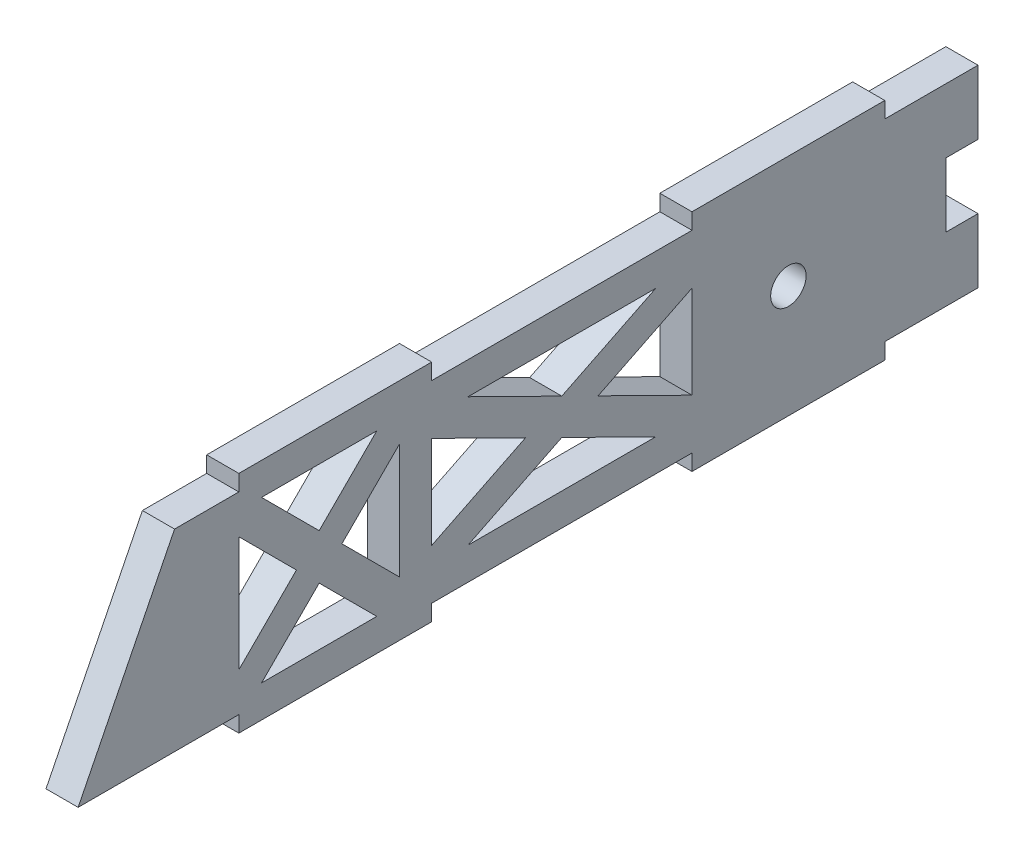
SolidWorks part; units mm, degrees
material "7050-T73510"
ref_plane "Front Plane" through (0, 0, 0) normal (0, 0, 1) x (1, 0, 0)
ref_plane "Top Plane" through (0, 0, 0) normal (0, 1, 0) x (1, 0, 0)
ref_plane "Right Plane" through (0, 0, 0) normal (1, 0, 0) x (0, 0, -1)
sketch "Sketch1" plane through (0, 0, 0) normal (1, 0, 0) x (0, 0, -1)
  line L1 (-177.8, -38.1) -> (177.8, -38.1)
  line L2 (-177.8, -38.1) -> (-177.8, 38.1)
  line L3 (-177.8, 38.1) -> (177.8, 38.1)
  line L4 (177.8, -38.1) -> (177.8, 38.1)
  line L5 (-177.8, -38.1) -> (177.8, 38.1) construction
  line L6 (-177.8, 38.1) -> (177.8, -38.1) construction
  point P0 (0, 0)
  dimension "D1" = 355.6
  dimension "D2" = 76.2
extrude "Boss-Extrude1" add sketch "Sketch1" along normal blind 12.7
sketch "Sketch2" plane through (12.7, 0, 0) normal (1, 0, 0) x (0, 0, -1)
  line L0 (-177.8, -38.1) -> (-139.7, 38.1)
  line L1 (177.8, 38.1) -> (-177.8, 38.1) construction
  dimension "D1" = 38.1
extrude "Cut-Extrude1" cut sketch "Sketch2" against normal through all and the other way through all
sketch "Sketch3" plane through (0, 0, 0) normal (-1, 0, 0) x (0, 0, 1)
  line L0 (177.8, -38.1) -> (-177.8, -38.1) construction
  line L1 (-140.97, -38.1) -> (-64.77, -38.1)
  line L2 (-140.97, -38.1) -> (-140.97, -44.45)
  line L3 (-140.97, -44.45) -> (-64.77, -44.45)
  line L4 (-64.77, -38.1) -> (-64.77, -44.45)
  line L5 (-177.8, -38.1) -> (-177.8, 38.1) construction
  line L6 (38.1, -38.1) -> (114.3, -38.1)
  line L7 (38.1, -38.1) -> (38.1, -44.45)
  line L8 (38.1, -44.45) -> (114.3, -44.45)
  line L9 (114.3, -38.1) -> (114.3, -44.45)
  line L10 (-177.8, 38.1) -> (139.7, 38.1) construction
  line L11 (-140.97, 38.1) -> (-64.77, 38.1)
  line L12 (-140.97, 38.1) -> (-140.97, 44.45)
  line L13 (-140.97, 44.45) -> (-64.77, 44.45)
  line L14 (-64.77, 38.1) -> (-64.77, 44.45)
  line L16 (38.1, 38.1) -> (114.3, 38.1)
  line L17 (38.1, 38.1) -> (38.1, 44.45)
  line L18 (38.1, 44.45) -> (114.3, 44.45)
  line L19 (114.3, 38.1) -> (114.3, 44.45)
  dimension "D1" = 76.2
  dimension "D2" = 6.35
  dimension "D3" = 76.2
  dimension "D4" = 6.35
  dimension "D5" = 36.83
  dimension "D6" = 215.9
  dimension "D7" = 76.2
  dimension "D8" = 6.35
  dimension "D9" = 6.35
  dimension "D10" = 76.2
extrude "Boss-Extrude2" add sketch "Sketch3" against normal blind 12.7
sketch "Sketch4" plane through (0, 0, 0) normal (-1, 0, 0) x (0, 0, 1)
  line L0 (-177.8, -38.1) -> (-177.8, 38.1) construction
  line L1 (-177.8, 12.7) -> (-165.1, 12.7)
  line L2 (-177.8, 12.7) -> (-177.8, -12.7)
  line L3 (-177.8, -12.7) -> (-165.1, -12.7)
  line L4 (-165.1, 12.7) -> (-165.1, -12.7)
  line L5 (-140.97, -38.1) -> (-177.8, -38.1) construction
  line L6 (-177.8, 38.1) -> (-140.97, 38.1) construction
  dimension "D1" = 25.4
  dimension "D2" = 25.4
  dimension "D3" = 12.7
extrude "Cut-Extrude2" cut sketch "Sketch4" against normal through all
sketch "Sketch5" plane through (0, 0, 0) normal (-1, 0, 0) x (0, 0, 1)
  line L0 (-165.1, -12.7) -> (-165.1, 12.7) construction
  line L1 (-140.97, -38.1) -> (-177.8, -38.1) construction
  circle A0 centre (-102.87, 0) radius 7
  dimension "D1" = 62.23
  dimension "D3" = 14
  dimension "D2" = 38.1
extrude "Cut-Extrude3" cut sketch "Sketch5" against normal through all
sketch "Sketch6" plane through (0, 0, 0) normal (-1, 0, 0) x (0, 0, 1)
  line L0 (38.1, -38.1) -> (-64.77, -38.1) construction
  line L1 (-64.77, 25.4) -> (38.1, 25.4)
  line L2 (-64.77, 25.4) -> (-64.77, -25.4)
  line L3 (-64.77, -25.4) -> (38.1, -25.4)
  line L4 (38.1, 25.4) -> (38.1, -25.4)
  line L5 (-64.77, 38.1) -> (38.1, 38.1) construction
  line L6 (38.1, 44.45) -> (38.1, 38.1) construction
  line L7 (-64.77, 38.1) -> (-64.77, 44.45) construction
  line L8 (-64.77, 25.4) -> (38.1, -25.4) construction
  line L9 (-64.77, -25.4) -> (38.1, 25.4) construction
  line L10 (-50.4288, -25.4) -> (-13.335, -7.0821)
  line L11 (23.7588, 25.4) -> (-13.335, 7.0821)
  line L12 (-50.4288, 25.4) -> (-13.335, 7.0821)
  line L13 (23.7588, -25.4) -> (-13.335, -7.0821)
  line L14 (1.0062, 0) -> (38.1, 18.3179)
  line L15 (-27.6762, 0) -> (-64.77, 18.3179)
  line L16 (1.0062, 0) -> (38.1, -18.3179)
  line L17 (-27.6762, 0) -> (-64.77, -18.3179)
  line L18 (38.1, -44.45) -> (114.3, -44.45) construction
  line L19 (50.8, 31.75) -> (114.3, 31.75)
  line L20 (50.8, 31.75) -> (50.8, -31.75)
  line L21 (50.8, -31.75) -> (114.3, -31.75)
  line L22 (114.3, 31.75) -> (114.3, -31.75)
  line L23 (114.3, 44.45) -> (38.1, 44.45) construction
  line L26 (114.3, 38.1) -> (114.3, 44.45) construction
  line L28 (50.8, -31.75) -> (114.3, 31.75) construction
  line L29 (114.3, -31.75) -> (50.8, 31.75) construction
  line L30 (59.7803, -31.75) -> (114.3, 22.7697)
  line L31 (50.8, -22.7697) -> (105.3197, 31.75)
  line L32 (114.3, -22.7697) -> (59.7803, 31.75)
  line L33 (105.3197, -31.75) -> (50.8, 22.7697)
  point P36 (114.3, 41.275)
  dimension "D1" = 12.7
  dimension "D2" = 12.7
  dimension "D3" = 12.7
  dimension "D4" = 12.7
  dimension "D5" = 12.7
  dimension "D6" = 12.7
  dimension "D7" = 12.7
  dimension "D8" = 0
  dimension "D9" = 12.7
  dimension "D10" = 12.7
extrude "Cut-Extrude4" cut sketch "Sketch6" against normal through all contours L3 L13 L10 | L17 L15 L2 | L1 L12 L11 | L14 L16 L4 | L21 L33 L30 | L32 L22 L30 | L31 L33 L20 | L32 L31 L19 region at (0, 19.294, -13.335) region at (0, 0, -52.4054) region at (0, 0, 25.7354) region at (0, -19.294, -13.335) region at (0, 24.1601, 82.55) region at (0, 0, 58.3899) region at (0, 0, 106.7101) region at (0, -24.1601, 82.55)
